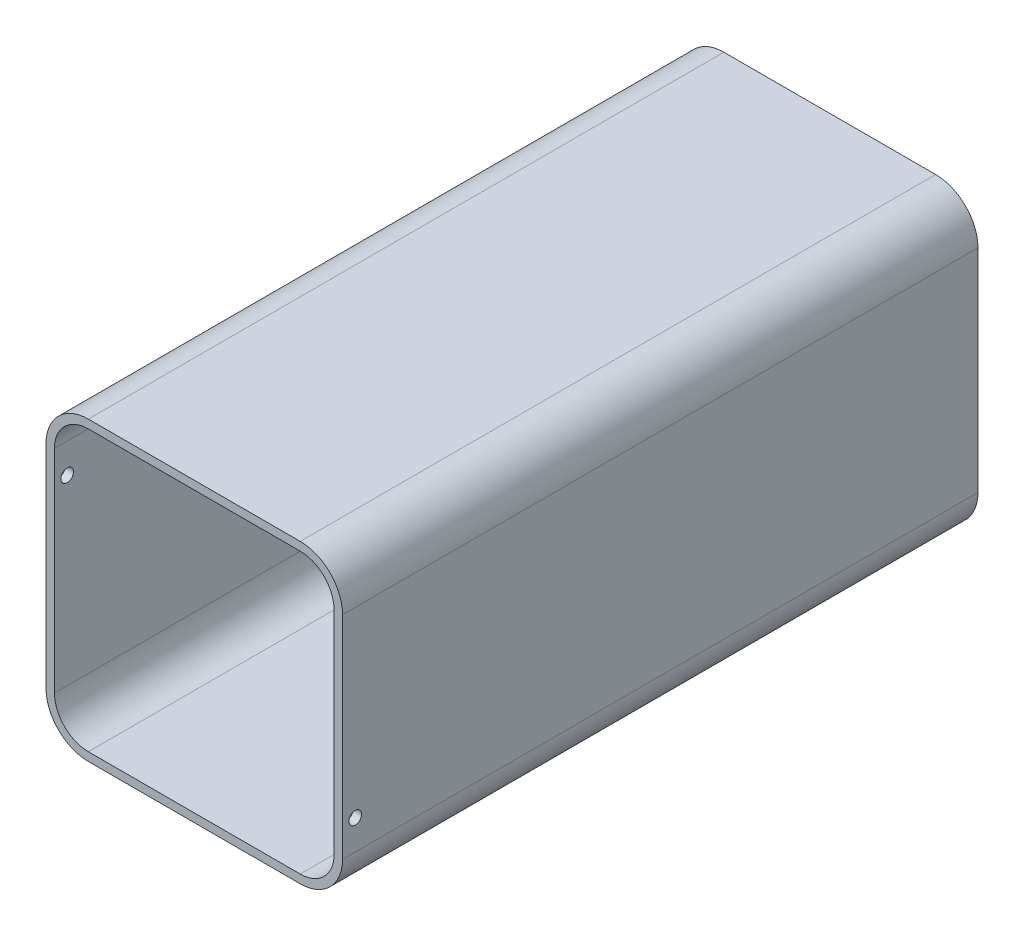
SolidWorks part; units mm, degrees
ref_plane "前视基准面" through (0, 0, 0) normal (0, 0, 1) x (1, 0, 0)
ref_plane "上视基准面" through (0, 0, 0) normal (0, 1, 0) x (1, 0, 0)
ref_plane "右视基准面" through (0, 0, 0) normal (1, 0, 0) x (0, 0, -1)
sketch "草图1" plane through (0, 0, 0) normal (0, 0, 1) x (1, 0, 0)
  line L0 (-28.3182, 20.4135) -> (-28.3182, -29.5865)
  line L1 (-18.3182, -39.5865) -> (31.6818, -39.5865)
  line L2 (41.6818, -29.5865) -> (41.6818, 20.4135)
  line L3 (31.6818, 30.4135) -> (-18.3182, 30.4135)
  arc A0 (41.6818, 20.4135) -> (31.6818, 30.4135) centre (31.6818, 20.4135) ccw
  arc A1 (31.6818, -39.5865) -> (41.6818, -29.5865) centre (31.6818, -29.5865) ccw
  arc A2 (-18.3182, -39.5865) -> (-28.3182, -29.5865) centre (-18.3182, -29.5865) cw
  arc A3 (-18.3182, 30.4135) -> (-28.3182, 20.4135) centre (-18.3182, 20.4135) ccw
  dimension "D1" = 10
  dimension "D2" = 70
  dimension "D3" = 70
extrude "凸台-拉伸1" add sketch "草图1" along normal blind 150
shell "抽壳1" thickness 2 removed face at (6.6818, -4.5865, 150)
sketch "草图2" plane through (0, 0, 0) normal (0, 0, -1) x (-1, 0, 0)
  line L0 (28.3182, -4.5865) -> (-46.3898, -4.5865) construction
  line L1 (28.3182, 20.4135) -> (28.3182, -29.5865) construction
  line L2 (-6.6818, 30.4135) -> (-6.6818, -48.7763) construction
  line L3 (-31.6818, 30.4135) -> (18.3182, 30.4135) construction
  line L4 (8.0704, -17.0865) -> (8.0704, 7.9135)
  line L5 (8.0704, 7.9135) -> (21.5704, 7.9135)
  line L6 (21.5704, 7.9135) -> (21.5704, -17.0865)
  line L7 (14.8204, 7.9135) -> (14.8204, 18.9778) construction
  line L8 (8.0704, -17.0865) -> (21.5704, -17.0865)
  line L9 (15.5704, 9.8135) -> (14.8204, 9.8135) construction
  circle A3 centre (15.3204, -18.4865) radius 1.1
  circle A4 centre (14.8204, 9.309) radius 1.1
  point P24 (8.0704, -4.5865)
  point P25 (21.5704, -4.5865)
  dimension "D1" = 27.8
  dimension "D4" = 13.9
  dimension "D2" = 25
  dimension "D3" = 13.5
extrude "切除-拉伸1" cut sketch "草图2" against normal blind 150
sketch "草图3" plane through (0, 0, 0) normal (0, 0, -1) x (-1, 0, 0)
  line L1 (-15.6247, 9.6062) -> (-27.5319, 9.6062)
  line L2 (-15.6247, 9.6062) -> (-15.6247, -20.1429)
  line L3 (-15.6247, -20.1429) -> (-27.5319, -20.1429)
  line L4 (-27.5319, 9.6062) -> (-27.5319, -20.1429)
extrude "切除-拉伸2" cut sketch "草图3" against normal blind 10
fillet "圆角1" radius 2 1 edges at (15.6247, 9.6062, 1) type face fillet first side face at (15.6247, -5.2683, 1) second side face at (21.5783, 9.6062, 1)
fillet "圆角2" radius 2 1 edges at (15.6247, -20.1429, 1) type face fillet first side face at (15.6247, -6.2683, 1) second side face at (21.5783, -20.1429, 1)
fillet "圆角3" radius 2 1 edges at (27.5319, -20.1429, 1) type face fillet first side face at (22.5783, -20.1429, 1) second side face at (27.5319, -5.2683, 1)
fillet "圆角4" radius 2 1 edges at (27.5319, 9.6062, 1) type face fillet first side face at (27.5319, -4.2683, 1) second side face at (22.5783, 9.6062, 1)
sketch "草图4" plane through (39.6818, 0, 0) normal (-1, 0, 0) x (0, 0, 1)
  line L0 (150, -29.5865) -> (150, 20.4135) construction
  line L1 (150, -29.5865) -> (2, -29.5865) construction
  circle A0 centre (147, -22.5865) radius 1.5
  dimension "D1" = 3
  dimension "D2" = 7
extrude "切除-拉伸3" cut sketch "草图4" against normal blind 7
sketch "草图5" plane through (-26.3182, 0, 0) normal (1, 0, 0) x (0, 0, -1)
  line L0 (-150, 20.4135) -> (-150, -29.5865) construction
  line L1 (-150, 20.4135) -> (-2, 20.4135) construction
  circle A0 centre (-147, 13.4135) radius 1.5
  dimension "D1" = 3
  dimension "D2" = 7
extrude "切除-拉伸4" cut sketch "草图5" against normal blind 7
